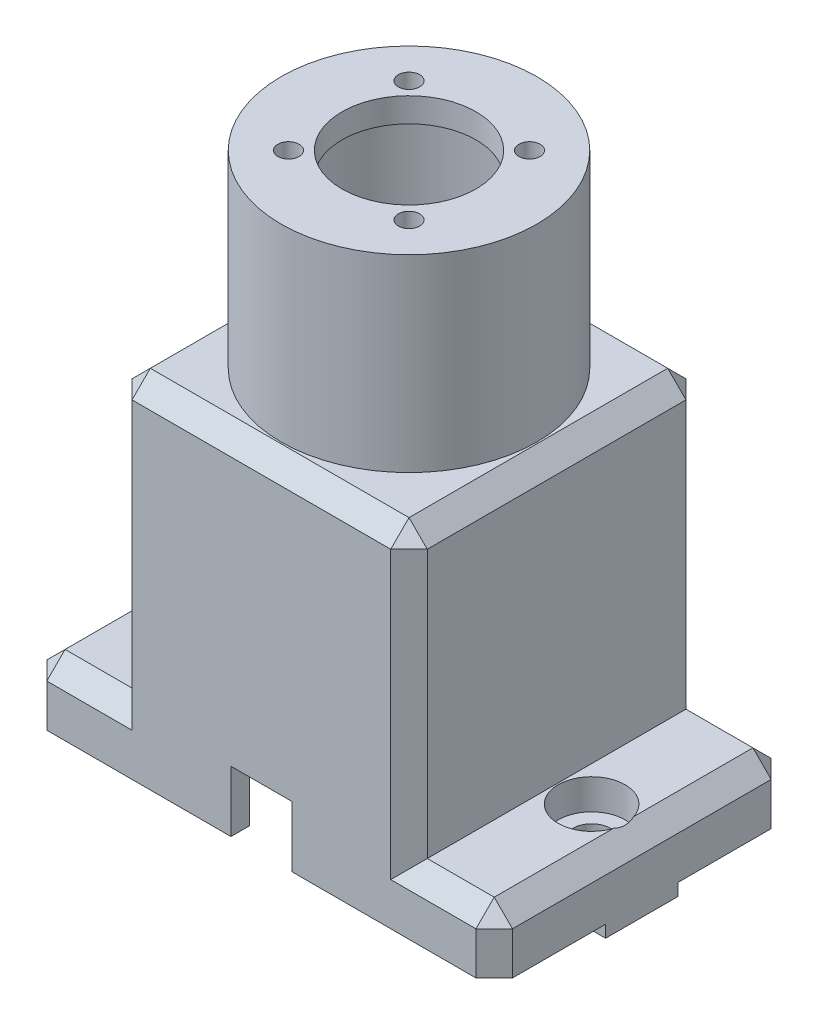
SolidWorks part; units mm, degrees
ref_plane "Płaszczyzna przednia" through (0, 0, 0) normal (0, 0, 1) x (1, 0, 0)
ref_plane "Płaszczyzna górna" through (0, 0, 0) normal (0, 1, 0) x (1, 0, 0)
ref_plane "Płaszczyzna prawa" through (0, 0, 0) normal (1, 0, 0) x (0, 0, -1)
sketch "Sketch1" plane through (0, 0, 0) normal (0, 1, 0) x (1, 0, 0)
  line L0 (0, 0) -> (0, -30.328) construction
  line L1 (0, 0) -> (19.9222, 19.9222) construction
  circle A0 centre (0, 0) radius 21
  circle A1 centre (0, 0) radius 14 construction
  circle A2 centre (-9.8995, -9.8995) radius 1.75
  circle A3 centre (-9.8995, 9.8995) radius 1.75
  circle A4 centre (9.8995, 9.8995) radius 1.75
  circle A5 centre (9.8995, -9.8995) radius 1.75
  point P19 (0, 0)
  dimension "D1" = 42
  dimension "D2" = 28
  dimension "D4" = 3.5
  dimension "D3" = 45
  dimension "D5" = 4
extrude "Boss-Extrude1" add sketch "Sketch1" along normal blind 31
sketch "Sketch3" plane through (0, 0, 0) normal (0, 1, 0) x (1, 0, 0)
  line L1 (24.25, -24.25) -> (-24.25, -24.25)
  line L2 (24.25, -24.25) -> (24.25, 24.25)
  line L3 (24.25, 24.25) -> (-24.25, 24.25)
  line L4 (-24.25, -24.25) -> (-24.25, 24.25)
  line L5 (24.25, -24.25) -> (-24.25, 24.25) construction
  line L6 (24.25, 24.25) -> (-24.25, -24.25) construction
  circle A0 centre (0, 0) radius 18.5
  point P0 (0, 0)
  dimension "D3" = 37
  dimension "D1" = 48.5
  dimension "D2" = 48.5
extrude "Boss-Extrude2" add sketch "Sketch3" against normal blind 57
sketch "Sketch4" plane through (0, 0, 0) normal (0, 1, 0) x (1, 0, 0)
  circle A0 centre (0, 0) radius 11
  dimension "D1" = 22
extrude "Cut-Extrude2" cut sketch "Sketch4" along normal through all both and the other way through all
sketch "Sketch5" plane through (0, 0, 0) normal (0, 0, 1) x (1, 0, 0)
  line L0 (-24.25, -57) -> (24.25, -57) construction
  line L1 (5, -67) -> (-5, -67)
  line L2 (5, -67) -> (5, -47)
  line L3 (5, -47) -> (-5, -47)
  line L4 (-5, -67) -> (-5, -47)
  line L5 (5, -67) -> (-5, -47) construction
  line L6 (5, -47) -> (-5, -67) construction
  point P0 (0, -57)
  dimension "D1" = 10
  dimension "D2" = 10
extrude "Cut-Extrude3" cut sketch "Sketch5" along normal through all
sketch "Sketch6" plane through (0, 0, 0) normal (0, 1, 0) x (1, 0, 0)
  line L0 (-24.25, 24.25) -> (-24.25, -24.25)
  line L8 (-24.25, 24.25) -> (-38.25, 24.25)
  line L9 (-24.25, -24.25) -> (-38.25, -24.25)
  line L10 (-38.25, 24.25) -> (-38.25, -24.25)
  line L11 (24.25, 24.25) -> (24.25, -24.25)
  line L12 (24.25, 24.25) -> (38.25, 24.25)
  line L13 (24.25, -24.25) -> (38.25, -24.25)
  line L14 (38.25, 24.25) -> (38.25, -24.25)
  dimension "D1" = 14
  dimension "D2" = 14
extrude "Boss-Extrude3" add sketch "Sketch6" along normal blind 10 from surface starting at face at (0, -57, 5.9764)
sketch "Sketch7" plane through (0, 0, 0) normal (0, 1, 0) x (1, 0, 0)
  line L0 (-38.25, -5.95) -> (38.25, -5.95)
  line L1 (-38.25, -5.95) -> (-38.25, 5.95)
  line L2 (38.25, -5.95) -> (38.25, 5.95)
  line L3 (-38.25, 5.95) -> (38.25, 5.95)
  line L4 (-38.25, 24.25) -> (-38.25, -24.25) construction
  line L5 (38.25, -24.25) -> (38.25, 24.25) construction
  dimension "D1" = 5.95
  dimension "D2" = 11.9
extrude "Boss-Extrude4" add sketch "Sketch7" against normal blind 2 from surface starting at face at (0, -57, 5.9764)
sketch "Sketch2" plane through (0, 0, 0) normal (0, 1, 0) x (1, 0, 0)
  circle A0 centre (0, 0) radius 18.5
  dimension "D1" = 37
extrude "Cut-Extrude1" cut sketch "Sketch2" along normal blind 27 and the other way through all
sketch "Sketch8" plane through (0, 0, 0) normal (0, 1, 0) x (1, 0, 0)
  line L0 (-37.7319, 0) -> (42.2681, 0) construction
  circle A0 centre (-30, 0) radius 3.1
  circle A1 centre (30, 0) radius 3.1
  dimension "D3" = 6.2
  dimension "D4" = 6.2
  dimension "D1" = 60
  dimension "D2" = 30
extrude "Cut-Extrude4" cut sketch "Sketch8" against normal through all
sketch "Sketch9" plane through (0, 0, 0) normal (0, 1, 0) x (1, 0, 0)
  circle A0 centre (-30, 0) radius 5.5
  circle A1 centre (30, 0) radius 5.5
  dimension "D1" = 11
  dimension "D2" = 11
extrude "Cut-Extrude5" cut sketch "Sketch9" against normal blind 5 from surface starting at face at (-30, -47, 3.1)
chamfer "Chamfer1" distance 3 angle 45 18 edges at (38.25, -52, 24.25) (38.25, -52, -24.25) (-38.25, -52, -24.25) (-38.25, -52, 24.25) (-31.25, -47, 24.25) (-38.25, -47, 0) (-31.25, -47, -24.25) (31.25, -47, -24.25) (38.25, -47, 0) (31.25, -47, 24.25) (24.25, 0, 0) (24.25, -23.5, 24.25) (0, 0, 24.25) (24.25, -23.5, -24.25) (0, 0, -24.25) (-24.25, -23.5, -24.25) (-24.25, 0, 0) (-24.25, -23.5, 24.25)
sketch "Sketch11" plane through (0, 0, 0) normal (0, 1, 0) x (1, 0, 0)
  line L1 (-21.25, -21.2) -> (21.25, -21.2)
  line L2 (-21.25, -21.2) -> (-21.25, 21.2)
  line L3 (-21.25, 21.2) -> (21.25, 21.2)
  line L4 (21.25, -21.2) -> (21.25, 21.2)
  line L5 (-21.25, -21.2) -> (21.25, 21.2) construction
  line L6 (-21.25, 21.2) -> (21.25, -21.2) construction
  point P0 (0, 0)
  dimension "D1" = 42.5
  dimension "D2" = 42.4
extrude "Cut-Extrude6" cut sketch "Sketch11" along normal blind 53 and the other way through all from surface starting at face at (-23.4556, -57, 16.8349)
